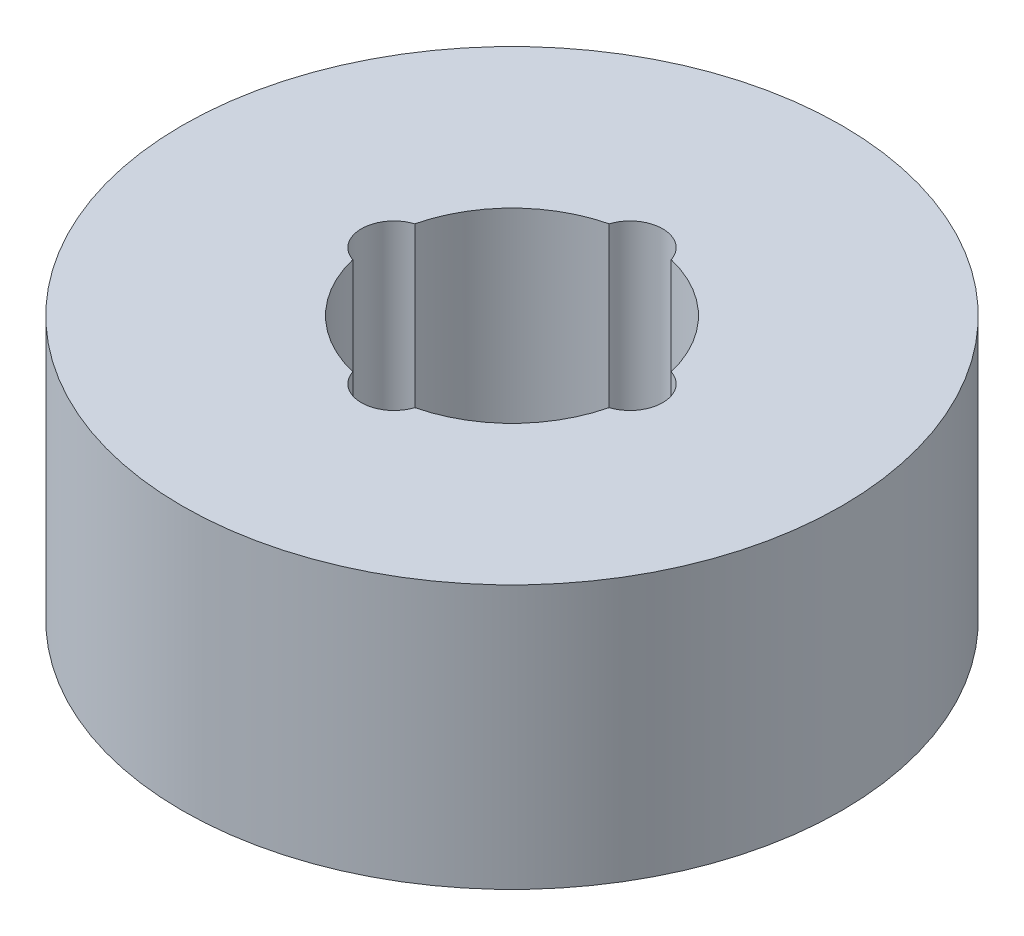
SolidWorks part; units mm, degrees
ref_plane "Front Plane" through (0, 0, 0) normal (0, 0, 1) x (1, 0, 0)
ref_plane "Top Plane" through (0, 0, 0) normal (0, 1, 0) x (1, 0, 0)
ref_plane "Right Plane" through (0, 0, 0) normal (1, 0, 0) x (0, 0, -1)
sketch "Sketch1" plane through (0, 0, 0) normal (0, 1, 0) x (1, 0, 0)
  circle A0 centre (0, 0) radius 25
  dimension "FLANGE_OD" = 50
extrude "Boss-Extrude1" add sketch "Sketch1" along normal blind 20
sketch "Sketch2" plane through (0, 0, 0) normal (0, 1, 0) x (1, 0, 0)
  circle A0 centre (0, 0) radius 10
  dimension "BORE_D" = 20
extrude "Cut-Extrude1" cut sketch "Sketch2" along normal through all
sketch "Sketch3" plane through (0, 20, 0) normal (0, 1, 0) x (1, 0, 0)
  circle A0 centre (0, 0) radius 8.9453 construction
  circle A1 centre (-8.9453, 0) radius 2.4779
  dimension "BOLT_D" = 4.9558
  dimension "BOLT_PCD" = 17.8906
extrude "Cut-Extrude2" cut sketch "Sketch3" against normal blind 18.0277
pattern_circular "CirPattern1" count 4 over 360 about axis through (0, 0, 0) along (0, 1, 0) of "Cut-Extrude2"
